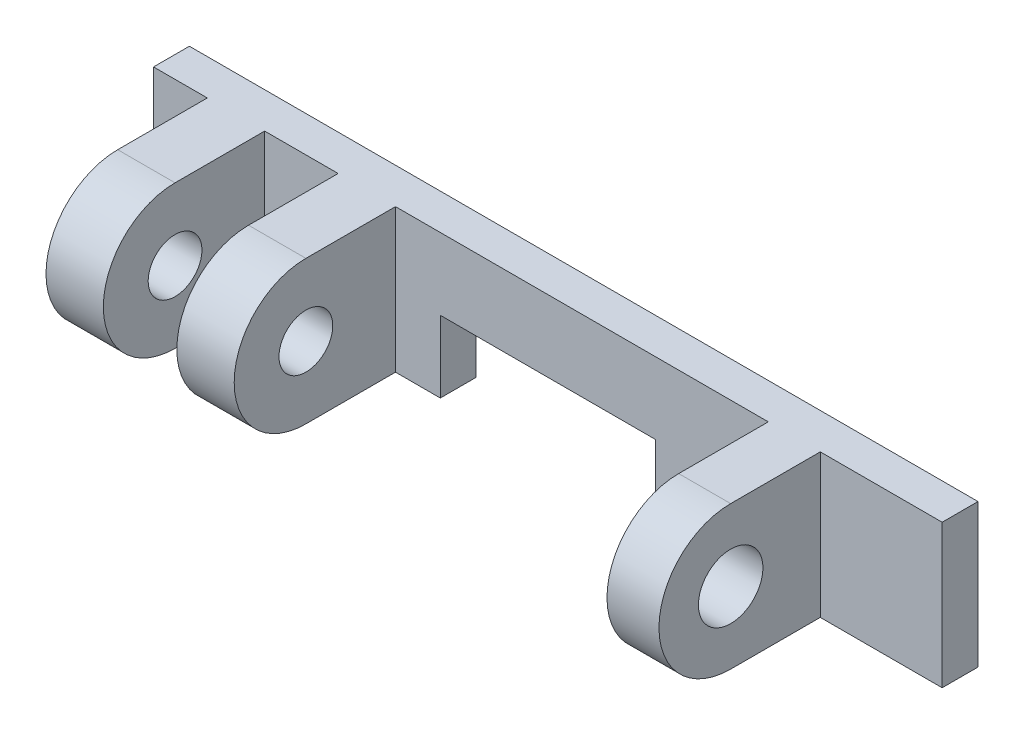
SolidWorks part; units mm, degrees
note: '?' marks a value the reader was unsure of. The reader was unsure of these and kept them because the rebuilt part matched: shared geometry of "Sketch1<3>", "Sketch1<5>", "Sketch1<4>", "Sketch1<6>".
other "link"
ref_plane "Front Plane" through (0, 0, 0) normal (0, 0, 1) x (1, 0, 0)
ref_plane "Top Plane" through (0, 0, 0) normal (0, 1, 0) x (1, 0, 0)
ref_plane "Right Plane" through (0, 0, 0) normal (1, 0, 0) x (0, 0, -1)
sketch "Sketch1" plane through (0, 0, 0) normal (1, 0, 0) x (0, 0, -1)
  line L0 (0, 2) -> (3.5, 2)
  line L1 (3.5, 2) -> (3.5, -2)
  line L2 (3.5, -2) -> (0, -2)
  line L3 (2.5, 2) -> (2.5, -2)
  line L4 (2.5, 0) -> (3.5, 0)
  circle A0 centre (0, 0) radius 0.9
  circle A2 centre (0, 0) radius 2
  circle A3 centre (0, 0) radius 0.75
  dimension "D1" = 1.8
  dimension "D2" = 4
  dimension "D4" = 0.5
  dimension "D5" = 1.5
  dimension "D3" = 1
sketch "Sketch2" plane through (0, 0, 0) normal (0, 1, 0) x (1, 0, 0)
  line L0 (-6, 2.5) -> (-6, -2) construction
  line L1 (-7.75, -2) -> (-7.75, 2.5) construction
  line L2 (-9.5, -2) -> (-9.5, 2.5) construction
  line L3 (-4.25, -2) -> (-4.25, 2.5) construction
  line L4 (11, 3.5) -> (-11, 3.5) construction
  line L5 (0, 3.5) -> (0, -2) construction
  line L6 (11, -2) -> (11, 3.5) construction
  line L7 (11, -2) -> (-11, -2) construction
  line L8 (-11, -2) -> (-11, 3.5) construction
  line L9 (4.25, -2) -> (4.25, 2.5) construction
  line L10 (-11, 2.5) -> (11, 2.5) construction
  line L11 (9.5, -2) -> (9.5, 2.5) construction
  line L13 (7.75, -2) -> (7.75, 2.5) construction
  line L14 (6, 2.5) -> (6, -2) construction
  line L16 (-3, 2.5) -> (-3, 3.5)
  line L17 (3, 2.5) -> (3, 3.5)
  point P19 (0, 2.5)
  dimension "D1" = 1.5
  dimension "D2" = 1.75
  dimension "D3" = 1.75
  dimension "D4" = 1.75
  dimension "D5" = 22
  dimension "D6" = 5.25
  dimension "D7" = 3.5
  dimension "D8" = 6
ref_axis "Axis1" through (-12.053, 0, 0) along (1, 0, 0)?
ref_axis "Axis2" through (0, -6.0998, 0) along (0, 1, 0)?
sketch "Sketch7" plane through (0, 0, 0) normal (0, 1, 0) x (1, 0, 0)
  line L0 (-11, 2.5) -> (-11, 3.5)
  line L1 (-11, 3.5) -> (11, 3.5)
  line L2 (11, 3.5) -> (11, 2.5)
  line L3 (11, 2.5) -> (7.6, 2.5)
  line L4 (7.6, 2.5) -> (7.6, -2)
  line L5 (7.6, -2) -> (6.15, -2)
  line L6 (6.15, -2) -> (6.15, 2.5)
  line L7 (6.15, 2.5) -> (-4.25, 2.5)
  line L8 (-4.25, 2.5) -> (-4.25, -2)
  line L9 (-4.25, -2) -> (-5.85, -2)
  line L10 (-5.85, -2) -> (-5.85, 2.5)
  line L11 (-5.85, 2.5) -> (-7.9, 2.5)
  line L12 (-7.9, 2.5) -> (-7.9, -2)
  line L13 (-7.9, -2) -> (-9.5, -2)
  line L14 (-9.5, -2) -> (-9.5, 2.5)
  line L15 (-9.5, 2.5) -> (-11, 2.5)
  line L16 (-7.75, -2) -> (-7.75, 2.5) construction
  line L17 (-6, 2.5) -> (-6, -2) construction
  line L18 (6, 2.5) -> (6, -2) construction
  line L19 (7.75, -2) -> (7.75, 2.5) construction
  dimension "D1" = 0.15
  dimension "D2" = 0.15
  dimension "D3" = 0.15
  dimension "D4" = 0.15
extrude "Boss-Extrude1" add sketch "Sketch1" along normal up to vertex (-7.9 mm away) from vertex at -9.5
extrude "Boss-Extrude2" add sketch "Sketch1<3>" along normal up to vertex (-4.25 mm away) from vertex at -5.85 separate body
sketch "Sketch1<3>" plane through (0, 0, 0) normal (1, 0, 0) x (0, 0, -1) same geometry as "Sketch1"
extrude "Boss-Extrude5" add sketch "Sketch1<5>" against normal up to vertex (-6.15 mm away) from vertex at 7.6 separate body contours A2 A0 | A2 L2 L3 L0 starting at point (7.6, 0, 2)
sketch "Sketch1<5>" plane through (0, 0, 0) normal (1, 0, 0) x (0, 0, -1) same geometry as "Sketch1"
extrude "Boss-Extrude3" add sketch "Sketch1<4>" against normal up to vertex (11 mm away) from vertex at 11 contours L0 L3 L2 L1 | L4 L3 L2 L1
sketch "Sketch1<4>" plane through (0, 0, 0) normal (1, 0, 0) x (0, 0, -1) same geometry as "Sketch1"
extrude "Cut-Extrude1" cut sketch "Sketch1<6>" against normal up to vertex (3 mm away) from vertex at 3 contours L4 L3 L2 L1 starting at point (3, 0, -2.5)
sketch "Sketch1<6>" plane through (0, 0, 0) normal (1, 0, 0) x (0, 0, -1) same geometry as "Sketch1"
equation "\"D4@Sketch2\"=\"D3@Sketch2\""
equation "\"D3@Sketch2\"=\"D2@Sketch2\""
equation "\"D2@Sketch7\"=\"D1@Sketch7\""
equation "\"D3@Sketch7\"=\"D2@Sketch7\""
equation "\"D4@Sketch7\"=\"D1@Sketch7\""
